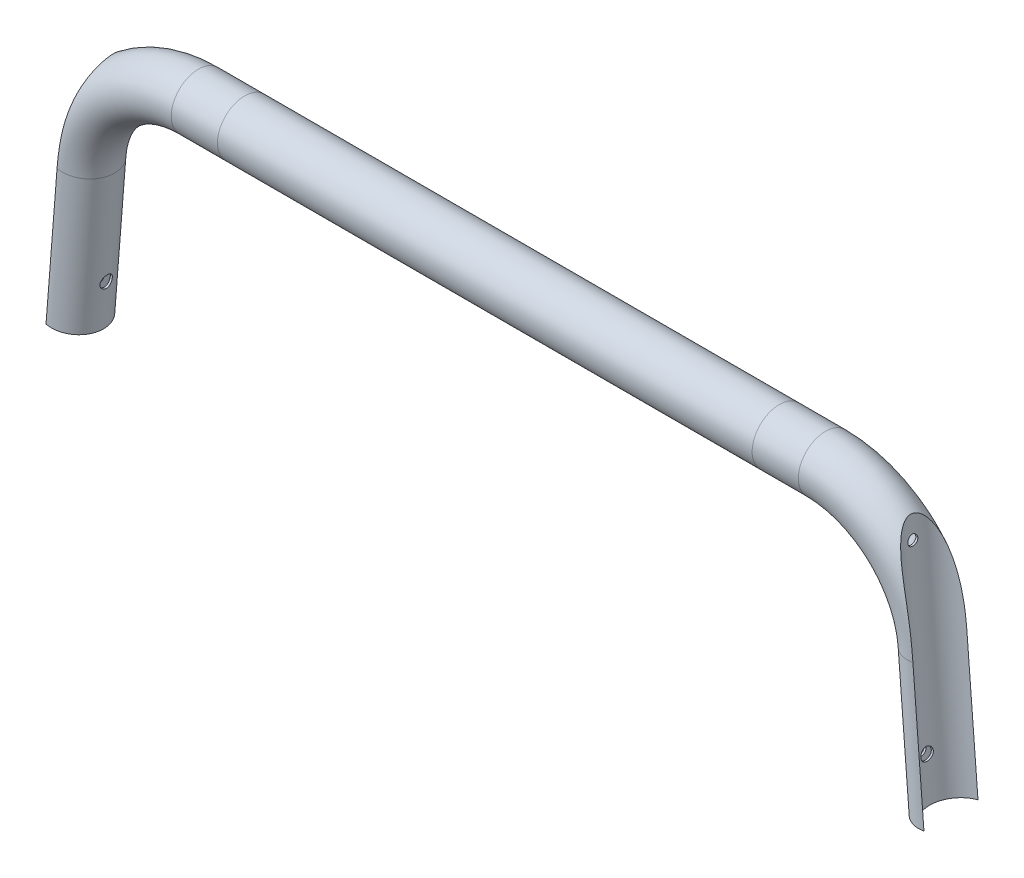
SolidWorks part; units mm, degrees
ref_plane "Front Plane" through (0, 0, 0) normal (0, 0, 1) x (1, 0, 0)
ref_plane "Top Plane" through (0, 0, 0) normal (0, 1, 0) x (1, 0, 0)
ref_plane "Right Plane" through (0, 0, 0) normal (1, 0, 0) x (0, 0, -1)
sketch "Sketch1" plane through (0, 0, 0) normal (0, 0, 1) x (1, 0, 0)
  line L0 (-108, 0) -> (108, 0)
  line L1 (0, 0) -> (0, -80) construction
  line L3 (-176, -98.2) -> (-171.5352, -41.4693)
  line L4 (-126.6739, 0) -> (-108, 0)
  line L5 (176, -98.2) -> (171.5352, -41.4693)
  line L6 (126.6739, 0) -> (108, 0)
  arc A0 (171.5352, -41.4693) -> (126.6739, 0) centre (126.6739, -45) ccw
  arc A1 (-126.6739, 0) -> (-171.5352, -41.4693) centre (-126.6739, -45) ccw
  point P4 (0, 0)
  point P11 (0, -80)
  dimension "D5" = 45
  dimension "D1" = 216
  dimension "D2" = 98.2
  dimension "D3" = 94.5
  dimension "D4" = 94.5
  dimension "D6" = 98.2
  dimension "D7" = 352
ref_plane "Plane1" through (-176, -98.2, 0) normal (-0.0785, -0.9969, 0) x (-0.9969, 0.0785, 0)
sketch "Sketch2" plane through (-176, -98.2, 0) normal (-0.0785, -0.9969, 0) x (-0.9969, 0.0785, 0)
  line L0 (-41.4693, 0) -> (0, 0) construction
  circle A0 centre (0, 0) radius 11
  circle A1 centre (0, 0) radius 10.2
  dimension "D1" = 0.8
sweep "Sweep1" add profiles "Sketch2" path "Sketch1"
sketch "Sketch3" plane through (8.7644, -111.3617, 0) normal (0.0785, -0.9969, 0) x (0.9969, 0.0785, 0)
  line L0 (167.7528, 0) -> (171.7528, 0) construction
  circle A0 centre (171.7528, 0) radius 11.2358
  dimension "D1" = 4
extrude "Cut-Extrude1" cut sketch "Sketch3" against normal through all
mirror "Mirror1" about plane through (0, 0, 0) normal (1, 0, 0) of "Cut-Extrude1"
sketch "Sketch6" plane through (8.7644, -111.3617, 0) normal (0.0785, -0.9969, 0) x (0.9969, 0.0785, 0)
  line L0 (167.7528, 0) -> (171.7528, 0) construction
  line L1 (169.0973, 10.9175) -> (166.6863, 10.9175)
  line L2 (169.0973, -10.9175) -> (167.984, -11.4305)
  arc A4 (166.6863, 10.9175) -> (167.984, -11.4305) centre (171.7528, 0) ccw
  circle A5 centre (171.7528, 0) radius 12.0358 construction
  arc A7 (169.0973, 10.9175) -> (169.0973, -10.9175) centre (171.7528, 0) ccw
  circle A8 centre (171.7528, 0) radius 11.2358 construction
  dimension "D1" = 0.8
extrude "Boss-Extrude1" add sketch "Sketch6" against normal up to next
mirror "Mirror2" about plane through (0, 0, 0) normal (1, 0, 0) of "Boss-Extrude1"
sketch "Sketch7" plane through (8.7644, -111.3617, 0) normal (0.0785, -0.9969, 0) x (0.9969, 0.0785, 0)
  line L0 (156.7528, 0) -> (167.7528, 0)
  arc A0 (169.0973, 10.9175) -> (169.0973, -10.9175) centre (167.7528, 0) ccw construction
ref_plane "Plane2" through (176, -98.2, 0) normal (0.9969, 0.0785, 0) x (0, 0, -1)
sketch "Sketch8" plane through (176, -98.2, 0) normal (0.9969, 0.0785, 0) x (0, 0, -1)
  line L0 (0, 0.0022) -> (0, 17.3022) construction
  circle A0 centre (0, 17.3022) radius 2.5
extrude "Cut-Extrude2" cut sketch "Sketch8" against normal up to surface (341.0156 mm away) up to face at (168.9548, -70.2134, 0)
mirror "Mirror3" about plane through (0, 0, 0) normal (1, 0, 0) of "Cut-Extrude2"
ref_plane "Plane3" through (180, 0, 0) normal (1, 0, 0) x (0, 0, -1)
sketch "Sketch9" plane through (180, 0, 0) normal (1, 0, 0) x (0, 0, -1)
  circle A0 centre (0, -9.5725) radius 2
extrude "Cut-Extrude3" cut sketch "Sketch9" against normal up to next
